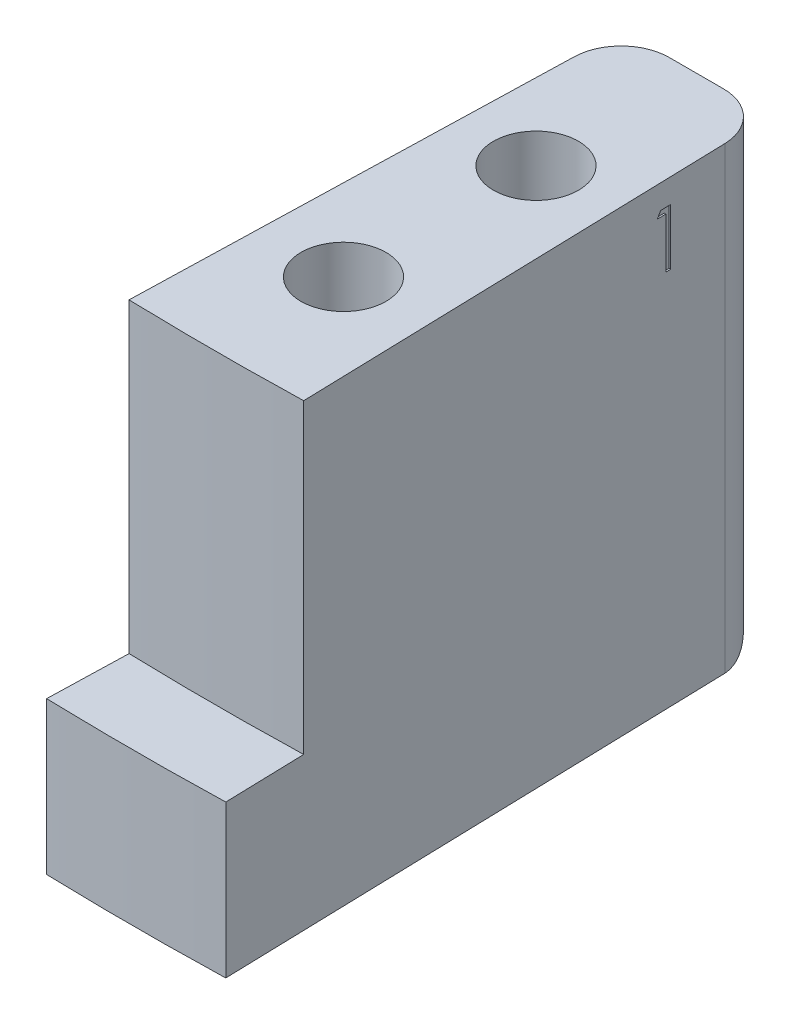
SolidWorks part; units mm, degrees
ref_plane "前视基准面" through (0, 0, 0) normal (0, 0, 1) x (1, 0, 0)
ref_plane "上视基准面" through (0, 0, 0) normal (0, 1, 0) x (1, 0, 0)
ref_plane "右视基准面" through (0, 0, 0) normal (1, 0, 0) x (0, 0, -1)
ref_axis "顶盖中心轴" through (0, -55, 0) along (0, 1, 0)
sketch "草图1" plane through (0, 0, 0) normal (0, 1, 0) x (1, 0, 0)
  line L0 (-4.7487, -170.0072) -> (-4.8586, -173.9402) construction
  line L1 (0, 0) -> (0, -125.794) construction
  line L3 (-4.6089, -165) -> (4.6089, -165)
  line L4 (-4.6089, -165) -> (-5.5843, -199.922)
  line L5 (4.6089, -165) -> (5.5843, -199.922)
  arc A0 (-5.4447, -194.924) -> (5.4447, -194.924) centre (0, 0) ccw
  arc A1 (-5.5843, -199.922) -> (5.5843, -199.922) centre (0, 0) ccw
  dimension "D1" = 1.6
  dimension "D2" = 195
  dimension "D4" = 200
  dimension "D3" = 165
extrude "主体" add sketch "草图1" along normal blind 28.6 contours L4 A0 L5 L3 region at (0, 0, 180.4033)
extrude "插销" add sketch "草图1<3>" along normal blind 9.5 contours L4 A1 L5 A0 region at (0, 0, 197.4849)
sketch "草图1<3>" plane through (0, 0, 0) normal (0, 1, 0) x (1, 0, 0) same geometry as "草图1"
ref_plane "对称面" through (0, 0, 0) normal (1, 0, 0) x (0, 0, -1)
fillet "圆角1" radius 3 3 edges at (-4.6089, 14.3, 165) (4.6089, 14.3, 165) (0, 0, 165)
hole_wizard "M5 间隙孔1" positions "草图4" profile "草图5" hole size "M5" standard "ISO" end condition up to next
sketch "草图4" plane through (0, 28.6, 0) normal (0, 1, 0) x (1, 0, 0)
  line L0 (0, -13.75) -> (0, 13.75) construction
  point P0 (0, -187)
  point P2 (0, -175)
  dimension "D1" = 175
  dimension "D2" = 187
sketch "草图5" plane through (0, 28.6, 187) normal (1, 0, 0) x (0, 0, 1)
  line L0 (0, 0) -> (0, 28.6)
  line L1 (0, 28.6) -> (2.65, 28.6)
  line L2 (2.65, 28.6) -> (2.65, 0)
  line L5 (2.65, 0) -> (0, 0)
  line L11 (0, -6.35) -> (0, 107.95) construction
  dimension "通孔孔直径" = 5.3
  dimension "通孔孔深度" = 28.6
sketch "草图6" plane through (0, 0, 0) normal (0, -1, 0) x (1, 0, 0)
  line L1 (0, 179.792) -> (-4.15, 177.396)
  line L2 (-4.15, 177.396) -> (-4.15, 172.604)
  line L3 (-4.15, 172.604) -> (0, 170.208)
  line L4 (0, 170.208) -> (4.15, 172.604)
  line L5 (4.15, 172.604) -> (4.15, 177.396)
  line L6 (4.15, 177.396) -> (0, 179.792)
  line L7 (0, 191.792) -> (-4.15, 189.396)
  line L8 (-4.15, 189.396) -> (-4.15, 184.604)
  line L9 (-4.15, 184.604) -> (0, 182.208)
  line L10 (0, 182.208) -> (4.15, 184.604)
  line L11 (4.15, 184.604) -> (4.15, 189.396)
  line L12 (4.15, 189.396) -> (0, 191.792)
  circle A0 centre (0, 175) radius 4.15 construction
  circle A1 centre (0, 187) radius 4.15 construction
  point P9 (0, 182.208)
  point P17 (0, 170.208)
  dimension "D1" = 8.3
  dimension "D2" = 8.3
extrude "切除-拉伸1" cut sketch "草图6" against normal blind 5
sketch "草图7" plane through (0, 0, 0) normal (0.9996, 0, -0.0279) x (-0.0279, 0, -0.9996)
  line L0 (-167.9817, 0.0012) -> (-167.9817, 28.6) construction
  line L1 (-167.9817, 28.6) -> (-195, 28.6) construction
  text T0 "1"
  point P1 (0, 0)
  dimension "D1" = 5
  dimension "D2" = 5
extrude "切除-拉伸2" cut sketch "草图7" against normal blind 0.1
